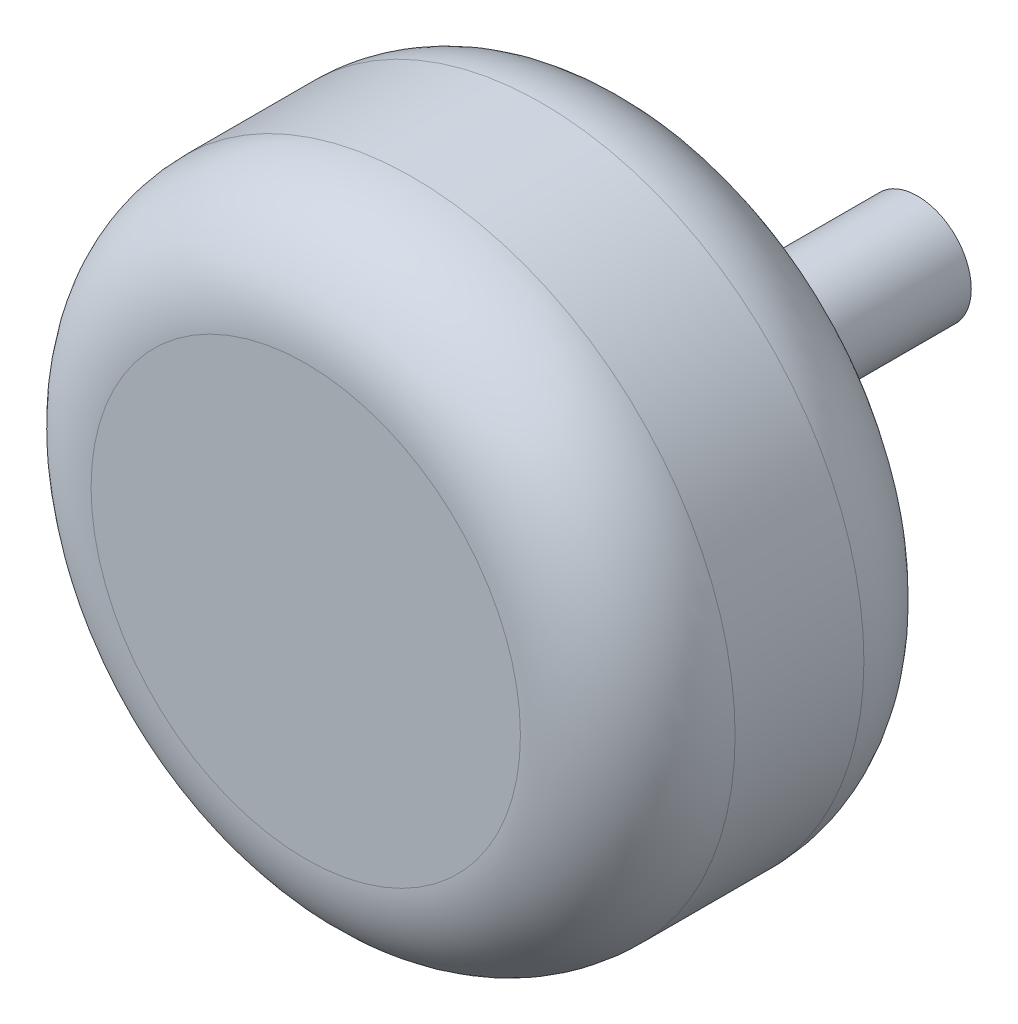
SolidWorks part; units mm, degrees
ref_plane "Спереди" through (0, 0, 0) normal (0, 0, 1) x (1, 0, 0)
ref_plane "Сверху" through (0, 0, 0) normal (0, 1, 0) x (1, 0, 0)
ref_plane "Справа" through (0, 0, 0) normal (1, 0, 0) x (0, 0, -1)
sketch "Эскиз1" plane through (0, 0, 0) normal (0, 0, 1) x (1, 0, 0)
  circle A0 centre (0, 0) radius 30
  dimension "D1" = 60
extrude "Бобышка-Вытянуть1" add sketch "Эскиз1" along normal blind 32
fillet "Скругление1" radius 10 2 edges at (30, 0, 0) (30, 0, 32)
sketch "Эскиз2" plane through (0, 0, 0) normal (0, 0, -1) x (-1, 0, 0)
  line L0 (-1.199, 2.75) -> (1.199, 2.75)
  line L7 (-1.199, -2.75) -> (1.199, -2.75)
  circle A0 centre (0, 0) radius 5
  arc A1 (-1.199, 2.75) -> (-1.199, -2.75) centre (0, 0) ccw
  arc A4 (1.199, -2.75) -> (1.199, 2.75) centre (0, 0) ccw
  dimension "D1" = 10
  dimension "D2" = 6
  dimension "D4" = 2.3979
  dimension "D5" = 2.3979
extrude "Бобышка-Вытянуть2" add sketch "Эскиз2" along normal blind 25
